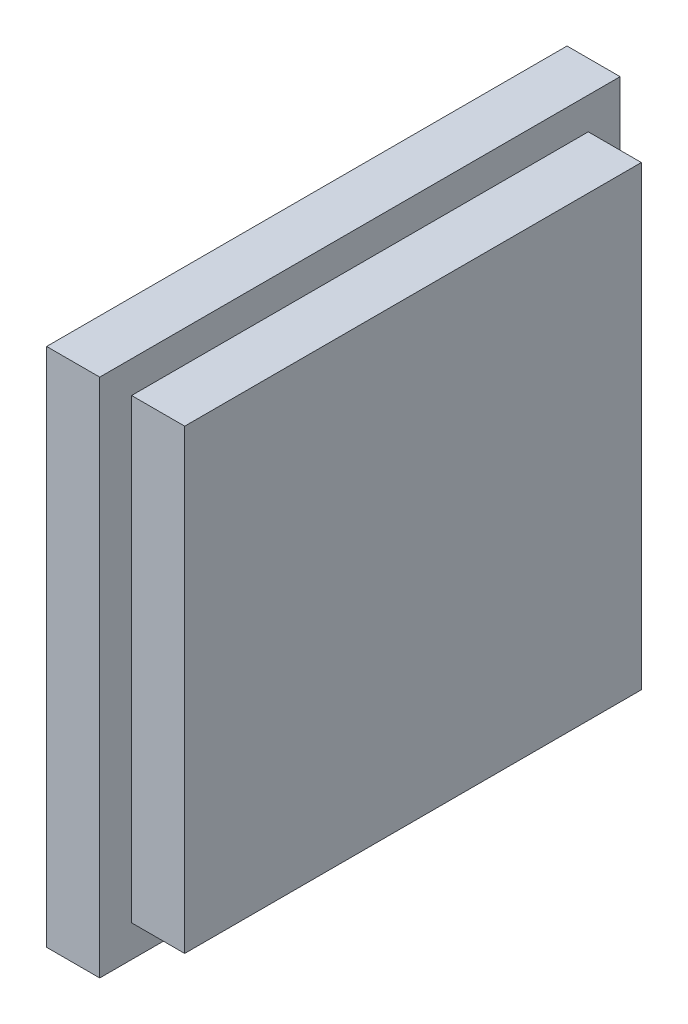
SolidWorks part; units mm, degrees
ref_plane "Front Plane" through (0, 0, 0) normal (0, 0, 1) x (1, 0, 0)
ref_plane "Top Plane" through (0, 0, 0) normal (0, 1, 0) x (1, 0, 0)
ref_plane "Right Plane" through (0, 0, 0) normal (1, 0, 0) x (0, 0, -1)
sketch "Sketch1" plane through (0, 0, 0) normal (1, 0, 0) x (0, 0, -1)
  line L1 (24.5, 24.5) -> (-24.5, 24.5)
  line L2 (24.5, 24.5) -> (24.5, -24.5)
  line L3 (24.5, -24.5) -> (-24.5, -24.5)
  line L4 (-24.5, 24.5) -> (-24.5, -24.5)
  line L5 (24.5, 24.5) -> (-24.5, -24.5) construction
  line L6 (24.5, -24.5) -> (-24.5, 24.5) construction
  point P0 (0, 0)
  dimension "D1" = 49
  dimension "D2" = 49
extrude "Boss-Extrude1" add sketch "Sketch1" along normal blind 5
sketch "Sketch3" plane through (5, 0, 0) normal (1, 0, 0) x (0, 0, -1)
  line L0 (24.5, 24.5) -> (-24.5, 24.5) construction
  line L1 (-21.5, 21.5) -> (21.5, 21.5)
  line L2 (-21.5, 21.5) -> (-21.5, -21.5)
  line L3 (-21.5, -21.5) -> (21.5, -21.5)
  line L4 (21.5, 21.5) -> (21.5, -21.5)
  line L5 (-21.5, 21.5) -> (21.5, -21.5) construction
  line L6 (-21.5, -21.5) -> (21.5, 21.5) construction
  line L7 (-24.5, 24.5) -> (-24.5, -24.5) construction
  point P0 (0, 0)
  dimension "D1" = 3
  dimension "D2" = 3
extrude "Boss-Extrude3" add sketch "Sketch3" along normal blind 5
